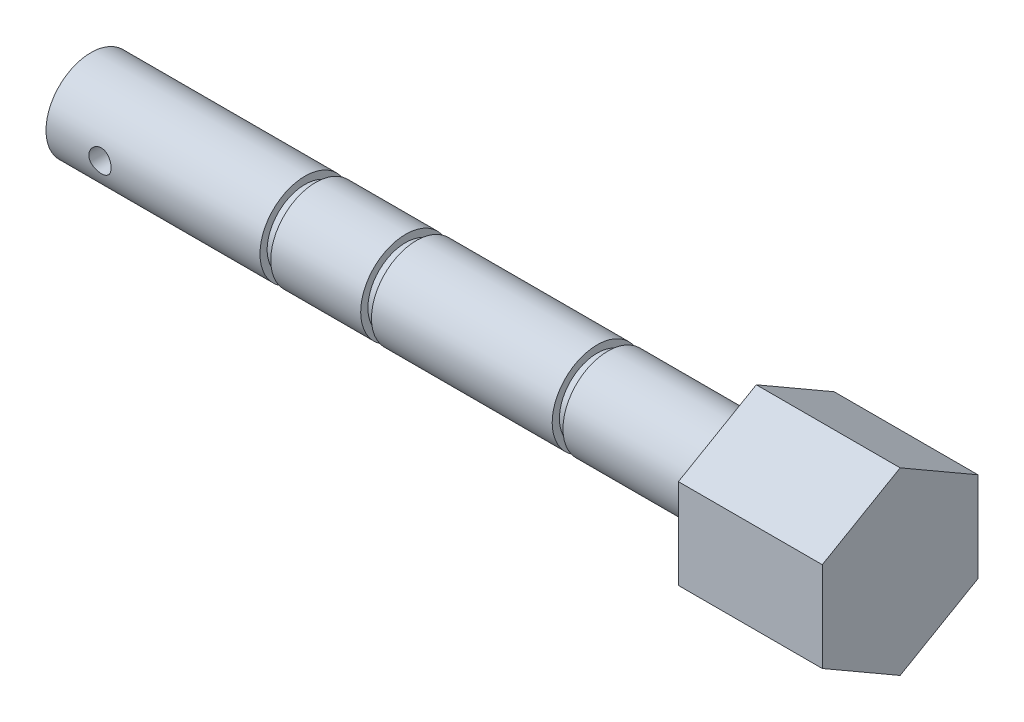
SolidWorks part; units mm, degrees
ref_plane "Front Plane" through (0, 0, 0) normal (0, 0, 1) x (1, 0, 0)
ref_plane "Top Plane" through (0, 0, 0) normal (0, 1, 0) x (1, 0, 0)
ref_plane "Right Plane" through (0, 0, 0) normal (1, 0, 0) x (0, 0, -1)
sketch "Sketch1" plane through (0, 0, 0) normal (1, 0, 0) x (0, 0, -1)
  circle A0 centre (0, 0) radius 3.175
extrude "Boss-Extrude2" add sketch "Sketch1" along normal blind 46.99 contours A0
sketch "Sketch2" plane through (46.99, 0, 0) normal (1, 0, 0) x (0, 0, -1)
  line L1 (-5.4993, 3.175) -> (-5.4993, -3.175)
  line L2 (-5.4993, -3.175) -> (0, -6.35)
  line L3 (0, -6.35) -> (5.4993, -3.175)
  line L4 (5.4993, -3.175) -> (5.4993, 3.175)
  line L5 (5.4993, 3.175) -> (0, 6.35)
  line L6 (0, 6.35) -> (-5.4993, 3.175)
  circle A0 centre (0, 0) radius 5.4993 construction
  dimension "D1" = 6.35
extrude "Boss-Extrude3" add sketch "Sketch2" along normal blind 10.16
sketch "Sketch3" plane through (0, 0, 0) normal (-1, 0, 0) x (0, 0, 1)
  circle A0 centre (0, 0) radius 1.778
  circle A1 centre (0, 0) radius 3.175
extrude "Cut-Extrude1" cut sketch "Sketch3" against normal blind 19.05
sketch "Sketch6" plane through (0, 0, 0) normal (-1, 0, 0) x (0, 0, 1)
  circle A0 centre (0, 0) radius 3.175
extrude "Boss-Extrude5" add sketch "Sketch6" against normal blind 49.022
sketch "Sketch7" plane through (0, 0, 0) normal (-1, 0, 0) x (0, 0, 1)
  line L1 (-0.4893, 0.7146) -> (-0.8635, -0.0664)
  line L2 (-0.8635, -0.0664) -> (-0.3742, -0.781)
  line L3 (-0.3742, -0.781) -> (0.4893, -0.7146)
  line L4 (0.4893, -0.7146) -> (0.8635, 0.0664)
  line L5 (0.8635, 0.0664) -> (0.3742, 0.781)
  line L6 (0.3742, 0.781) -> (-0.4893, 0.7146)
  circle A0 centre (0, 0) radius 0.75 construction
extrude "Cut-Extrude5" cut sketch "Sketch7" against normal blind 20.32
sketch "Sketch9" plane through (0, 0, 0) normal (-1, 0, 0) x (0, 0, 1)
  circle A0 centre (0, 0) radius 0.866
extrude "Cut-Extrude7" cut sketch "Sketch9" against normal blind 20.32 contours A0
sketch "Sketch10" plane through (0, 0, 5.4993) normal (0, 0, 1) x (1, 0, 0)
  line L0 (0, -3.175) -> (46.99, -3.175) construction
  line L1 (0, 3.175) -> (0, -3.175) construction
  circle A0 centre (3.81, 0) radius 0.7874
  dimension "D1" = 1.5748
  dimension "D2" = 3.81
  dimension "D3" = 3.175
extrude "Cut-Extrude8" cut sketch "Sketch10" against normal blind 5.334 contours A0
ref_plane "Plane1" through (36.5125, 0, 0) normal (-1, 0, 0) x (0, 0, 1)
sketch "Sketch11" plane through (36.5125, 0, 0) normal (-1, 0, 0) x (0, 0, 1)
  circle A0 centre (0, 0) radius 2.667
  circle A1 centre (0, 0) radius 3.175
  dimension "D1" = 5.334
  dimension "D2" = 6.35
extrude "Cut-Extrude9" cut sketch "Sketch11" along normal blind 0.762
ref_plane "Plane2" through (15.875, 0, 0) normal (-1, 0, 0) x (0, 0, 1)
sketch "Sketch12" plane through (15.875, 0, 0) normal (-1, 0, 0) x (0, 0, 1)
  circle A0 centre (0, 0) radius 2.667
  circle A1 centre (0, 0) radius 3.175
  dimension "D1" = 5.334
  dimension "D2" = 6.35
extrude "Cut-Extrude10" cut sketch "Sketch12" along normal blind 0.762
ref_plane "Plane3" through (22.987, 0, 0) normal (-1, 0, 0) x (0, 0, 1)
sketch "Sketch13" plane through (22.987, 0, 0) normal (-1, 0, 0) x (0, 0, 1)
  circle A0 centre (0, 0) radius 2.667
  circle A1 centre (0, 0) radius 3.175
  dimension "D1" = 5.334
  dimension "D2" = 6.35
extrude "Cut-Extrude12" cut sketch "Sketch13" along normal blind 0.762
